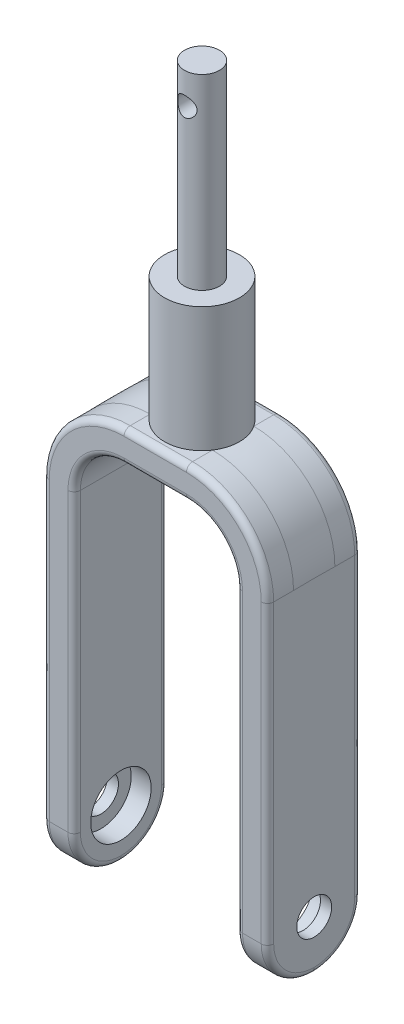
SolidWorks part; units mm, degrees
ref_plane "前视基准面" through (0, 0, 0) normal (0, 0, 1) x (1, 0, 0)
ref_plane "上视基准面" through (0, 0, 0) normal (0, 1, 0) x (1, 0, 0)
ref_plane "右视基准面" through (0, 0, 0) normal (1, 0, 0) x (0, 0, -1)
sketch "草图1" plane through (0, 0, 0) normal (0, 1, 0) x (1, 0, 0)
  line L1 (18, 7.5) -> (-18, 7.5)
  line L2 (18, 7.5) -> (18, -7.5)
  line L3 (18, -7.5) -> (-18, -7.5)
  line L4 (-18, 7.5) -> (-18, -7.5)
  line L5 (18, 7.5) -> (-18, -7.5) construction
  line L6 (18, -7.5) -> (-18, 7.5) construction
  point P0 (0, 0)
extrude "凸台-拉伸1" add sketch "草图1" against normal blind 68
sketch "草图2" plane through (0, 0, 0) normal (0, 1, 0) x (1, 0, 0)
  circle A0 centre (0, 0) radius 6
extrude "凸台-拉伸2" add sketch "草图2" along normal blind 20
sketch "草图7" plane through (0, 20, 0) normal (0, 1, 0) x (1, 0, 0)
  circle A0 centre (0, 0) radius 2.8
extrude "凸台-拉伸3" add sketch "草图7" along normal blind 30
sketch "草图8" plane through (0, 0, 0) normal (0, 0, 1) x (1, 0, 0)
  line L0 (0, 20) -> (0, 45) construction
  line L1 (6, 20) -> (-6, 20) construction
  circle A1 centre (0, 45) radius 1.55
extrude "切除-拉伸5" cut sketch "草图8" against normal through all both and the other way through all
sketch "草图3" plane through (0, 0, 7.5) normal (0, 0, 1) x (1, 0, 0)
  line L0 (-18, -68) -> (18, -68) construction
  line L1 (-13, -68) -> (13, -68)
  line L2 (-13, -68) -> (-13, -5)
  line L3 (-13, -5) -> (13, -5)
  line L4 (13, -68) -> (13, -5)
extrude "切除-拉伸1" cut sketch "草图3" against normal through all
fillet "圆角1" radius 8 2 edges at (13, -5, 0) (-13, -5, 0)
fillet "圆角5" radius 13 2 edges at (18, 0, 0) (-18, 0, 0)
fillet "圆角3" radius 7.5 4 edges at (15.5, -68, -7.5) (15.5, -68, 7.5) (-15.5, -68, -7.5) (-15.5, -68, 7.5)
fillet "圆角2" radius 1 28 edges at (-18, -36.75, -7.5) (0, 0, -7.5) (18, -36.75, -7.5) (18, -36.75, 7.5) (0, 0, 7.5) (-18, -36.75, 7.5) (-10.6569, -7.3431, 7.5) (0, -5, 7.5) (10.6569, -7.3431, 7.5) (13, -36.75, 7.5) (13, -36.75, -7.5) (10.6569, -7.3431, -7.5) (0, -5, -7.5) (-10.6569, -7.3431, -7.5) (-13, -36.75, -7.5) (-13, -36.75, 7.5) (13, -65.8033, 5.3033) (13, -65.8033, -5.3033) (-13, -65.8033, -5.3033) (-13, -65.8033, 5.3033) (-18, -65.8033, 5.3033) (-18, -65.8033, -5.3033) (18, -65.8033, -5.3033) (18, -65.8033, 5.3033) (-14.1924, -3.8076, -7.5) (14.1924, -3.8076, -7.5) (14.1924, -3.8076, 7.5) (-14.1924, -3.8076, 7.5)
sketch "草图4" plane through (18, 0, 0) normal (1, 0, 0) x (0, 0, -1)
  circle A0 centre (0, -60) radius 2.8
extrude "切除-拉伸2" cut sketch "草图4" against normal through all
sketch "草图6" plane through (13, 0, 0) normal (1, 0, 0) x (0, 0, -1)
  circle A0 centre (0, -60) radius 4.85
extrude "切除-拉伸4" cut sketch "草图6" along normal blind 3.2
mirror "镜向1" about plane through (0, 0, 0) normal (1, 0, 0) of "切除-拉伸4"
